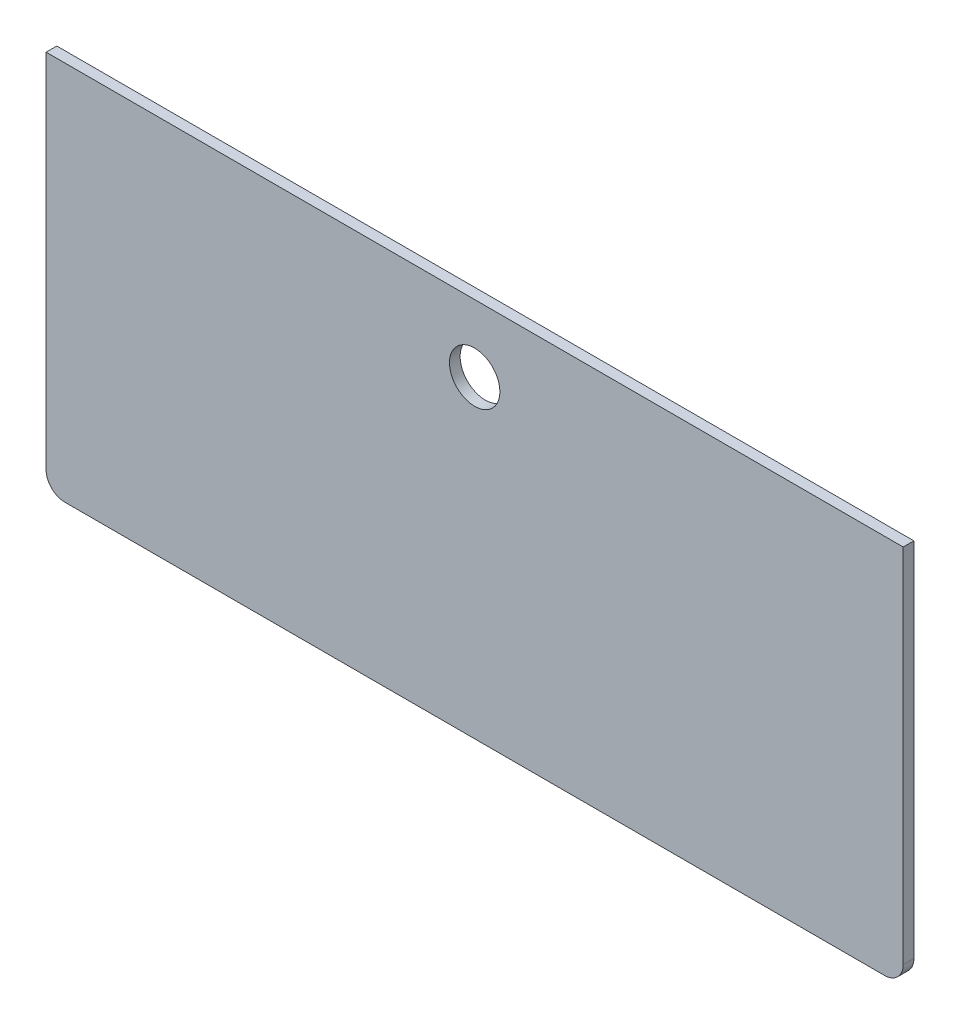
SolidWorks part; units mm, degrees
material "5052-H32"
ref_plane "Front Plane" through (0, 0, 0) normal (0, 0, 1) x (1, 0, 0)
ref_plane "Top Plane" through (0, 0, 0) normal (0, 1, 0) x (1, 0, 0)
ref_plane "Right Plane" through (0, 0, 0) normal (1, 0, 0) x (0, 0, -1)
sketch "Sketch1" plane through (0, 0, 0) normal (0, 0, 1) x (1, 0, 0)
  line L0 (-151.7654, 27.1868) -> (-151.7654, -85.9882)
  line L1 (-151.7654, -85.9882) -> (103.2346, -85.9882)
  line L2 (103.2346, -85.9882) -> (103.2346, 27.1868)
  line L3 (103.2346, 27.1868) -> (-151.7654, 27.1868)
  line L4 (-24.2654, 27.1868) -> (-24.2654, 7.1868) construction
  circle A0 centre (-24.2654, 7.1868) radius 7.5
  dimension "D4" = 15
  dimension "D1" = 113.175
  dimension "D2" = 255
  dimension "D3" = 20
extrude "Boss-Extrude1" add sketch "Sketch1" along normal blind 3.175
fillet "Fillet1" radius 5.5562 2 edges at (-151.7654, -85.9882, 1.5875) (103.2346, -85.9882, 1.5875)
equation "\"L\"= 400"
equation "\"W\"= 255"
equation "\"H\"= 110"
equation "\"Compartment Width\"= 80"
equation "\"T\"= 4.7625 * 2 / 3"
equation "\"Inside Fillet Radius\"= 5.55625"
equation "\"D1@Boss-Extrude1\"=\"T\""
equation "\"D1@Fillet1\"=\"Inside Fillet Radius\""
equation "\"Hole\"=15"
equation "\"D4@Sketch1\"=\"Hole\""
equation "\"D2@Sketch1\"=\"W\""
equation "\"D1@Sketch1\"=\"H\"+\"T\""
